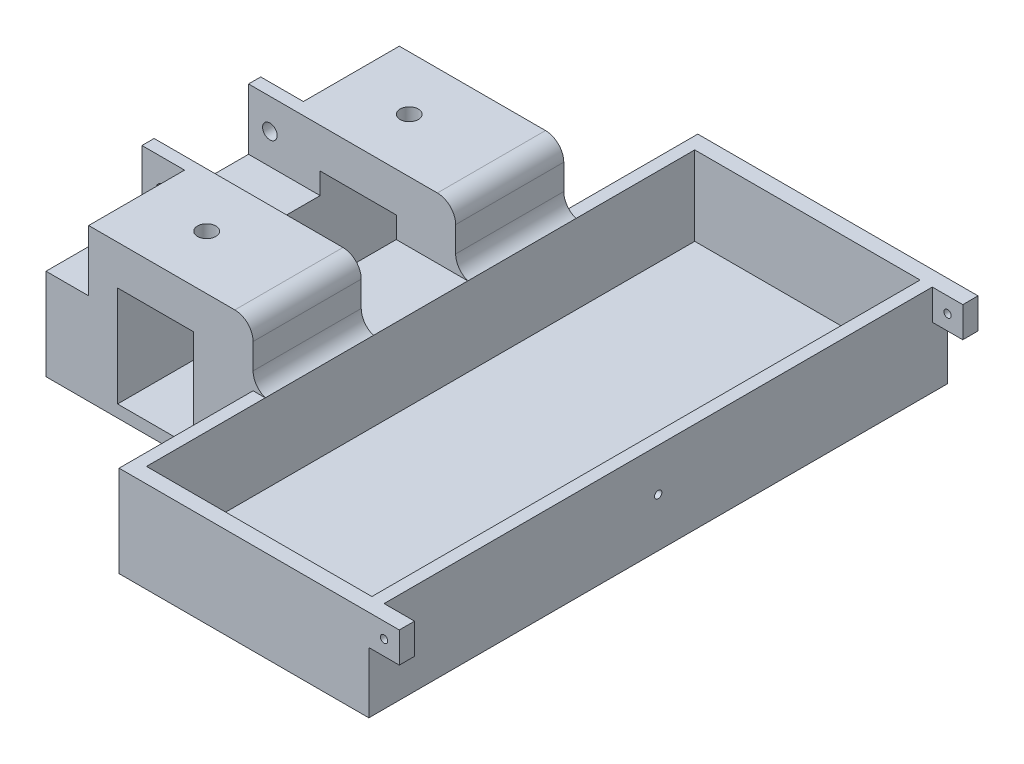
SolidWorks part; units mm, degrees
ref_plane "Front Plane" through (0, 0, 0) normal (0, 0, 1) x (1, 0, 0)
ref_plane "Top Plane" through (0, 0, 0) normal (0, 1, 0) x (1, 0, 0)
ref_plane "Right Plane" through (0, 0, 0) normal (1, 0, 0) x (0, 0, -1)
sketch "Sketch1" plane through (0, 0, 0) normal (0, 1, 0) x (1, 0, 0)
  line L1 (-37.5, -47.5) -> (37.5, -47.5)
  line L2 (-37.5, -47.5) -> (-37.5, 47.5)
  line L3 (-37.5, 47.5) -> (37.5, 47.5)
  line L4 (37.5, -47.5) -> (37.5, 47.5)
  line L5 (-37.5, -47.5) -> (37.5, 47.5) construction
  line L6 (-37.5, 47.5) -> (37.5, -47.5) construction
  point P0 (0, 0)
  dimension "D1" = 75
  dimension "D2" = 95
extrude "Boss-Extrude1" add sketch "Sketch1" along normal blind 15
sketch "Sketch2" plane through (37.5, 0, 0) normal (1, 0, 0) x (0, 0, -1)
  line L0 (47.5, 15) -> (47.5, 0) construction
  line L1 (-47.5, 15) -> (47.5, 15)
  line L2 (-47.5, 15) -> (-47.5, 10)
  line L3 (-47.5, 10) -> (47.5, 10)
  line L4 (47.5, 15) -> (47.5, 10)
  dimension "D1" = 5
extrude "Boss-Extrude2" add sketch "Sketch2" along normal blind 5
sketch "Sketch3" plane through (0, 0, -47.5) normal (0, 0, -1) x (-1, 0, 0)
  line L0 (-42.5, 10) -> (-42.5, 15) construction
  circle A0 centre (-40, 12.4586) radius 0.6
  point P2 (-42.5, 12.5)
  dimension "D1" = 2.5
extrude "Cut-Extrude1" cut sketch "Sketch3" against normal blind 100
sketch "Sketch4" plane through (0, 15, 0) normal (0, 1, 0) x (1, 0, 0)
  line L0 (42.5, 47.5) -> (42.5, -47.5) construction
  line L1 (42.5, -45) -> (37.5, -45)
  line L2 (42.5, -45) -> (42.5, 45)
  line L3 (42.5, 45) -> (37.5, 45)
  line L4 (37.5, -45) -> (37.5, 45)
  dimension "D1" = 5
  dimension "D2" = 2.5
  dimension "D3" = 2.5
extrude "Cut-Extrude2" cut sketch "Sketch4" against normal blind 100
sketch "Sketch5" plane through (0, 0, -47.5) normal (0, 0, -1) x (-1, 0, 0)
  line L0 (-37.5, 0) -> (37.5, 0) construction
  line L1 (37.5, 15) -> (3.5, 15)
  line L2 (37.5, 15) -> (37.5, 0)
  line L3 (37.5, 0) -> (3.5, 0)
  line L4 (3.5, 15) -> (3.5, 0)
  dimension "D1" = 34
extrude "Cut-Extrude3" cut sketch "Sketch5" against normal blind 22
sketch "Sketch6" plane through (0, 0, 47.5) normal (0, 0, 1) x (1, 0, 0)
  line L0 (-37.5, 0) -> (37.5, 0) construction
  line L1 (-37.5, 15) -> (-3.5, 15)
  line L2 (-37.5, 15) -> (-37.5, 0)
  line L3 (-37.5, 0) -> (-3.5, 0)
  line L4 (-3.5, 15) -> (-3.5, 0)
  dimension "D1" = 34
extrude "Cut-Extrude4" cut sketch "Sketch6" against normal blind 22
sketch "Sketch7" plane through (0, 15, 0) normal (0, 1, 0) x (1, 0, 0)
  line L0 (-3.5, -25.5) -> (-3.5, -47.5) construction
  line L1 (-1.5, -45) -> (35.5, -45)
  line L2 (-1.5, -45) -> (-1.5, 45)
  line L3 (-1.5, 45) -> (35.5, 45)
  line L4 (35.5, -45) -> (35.5, 45)
  line L5 (-3.5, -47.5) -> (42.5, -47.5) construction
  line L6 (42.5, 47.5) -> (-3.5, 47.5) construction
  point P8 (37.5, 45)
  dimension "D1" = 2
  dimension "D2" = 2.5
  dimension "D3" = 2.5
  dimension "D4" = 2
extrude "Cut-Extrude5" cut sketch "Sketch7" against normal blind 13
sketch "Sketch10" plane through (0, 15, 0) normal (0, 1, 0) x (1, 0, 0)
  line L1 (-37.5, 25.5) -> (-3.5, 25.5)
  line L2 (-37.5, 25.5) -> (-37.5, -25.5)
  line L3 (-37.5, -25.5) -> (-3.5, -25.5)
  line L4 (-3.5, 25.5) -> (-3.5, -25.5)
extrude "Boss-Extrude3" add sketch "Sketch10" along normal blind 10
sketch "Sketch11" plane through (0, 0, 25.5) normal (0, 0, 1) x (1, 0, 0)
  line L0 (-37.5, 0) -> (-3.5, 0) construction
  line L1 (-25.75, 2) -> (-13.25, 2)
  line L2 (-25.75, 2) -> (-25.75, 18.5)
  line L3 (-25.75, 18.5) -> (-13.25, 18.5)
  line L4 (-13.25, 2) -> (-13.25, 18.5)
  line L5 (-37.5, 25) -> (-37.5, 0) construction
  dimension "D1" = 12.5
  dimension "D2" = 16.5
  dimension "D3" = 2
  dimension "D4" = 11.75
extrude "Cut-Extrude6" cut sketch "Sketch11" against normal blind 100
sketch "Sketch12" plane through (-37.5, 0, 0) normal (-1, 0, 0) x (0, 0, 1)
  line L4 (7.75, 25) -> (7.75, 15)
  line L8 (-7.75, 25) -> (-7.75, 15)
  line L9 (-7.75, 15) -> (7.75, 15)
  line L11 (-7.75, 25) -> (7.75, 25)
  dimension "D1" = 15.5
  dimension "D2" = 10
extrude "Cut-Extrude8" cut sketch "Sketch12" against normal blind 100
sketch "Sketch13" plane through (-37.5, 0, 0) normal (-1, 0, 0) x (0, 0, 1)
  line L1 (-25.5, 25) -> (-9.75, 25)
  line L2 (-25.5, 25) -> (-25.5, 15)
  line L3 (-25.5, 15) -> (-9.75, 15)
  line L4 (-9.75, 25) -> (-9.75, 15)
  dimension "D1" = 15.75
extrude "Cut-Extrude9" cut sketch "Sketch13" against normal blind 7
sketch "Sketch14" plane through (-37.5, 0, 0) normal (-1, 0, 0) x (0, 0, 1)
  line L1 (25.5, 25) -> (9.75, 25)
  line L2 (25.5, 25) -> (25.5, 15)
  line L3 (25.5, 15) -> (9.75, 15)
  line L4 (9.75, 25) -> (9.75, 15)
  dimension "D1" = 10
  dimension "D2" = 2
extrude "Cut-Extrude10" cut sketch "Sketch14" against normal blind 7
sketch "Sketch15" plane through (0, 0, 9.75) normal (0, 0, 1) x (1, 0, 0)
  line L0 (-30.5, 15) -> (-37.5, 15) construction
  line L1 (-30.5, 25) -> (-30.5, 15) construction
  circle A0 centre (-34, 20) radius 1.2
  point P6 (-31.5863, 18.7429)
  dimension "D1" = 5
  dimension "D2" = 3.5
extrude "Cut-Extrude11" cut sketch "Sketch15" against normal blind 100
sketch "Sketch16" plane through (0, 2, 0) normal (0, 1, 0) x (1, 0, 0)
  line L0 (-1.5, -45) -> (35.5, -45) construction
  line L1 (33.5, -43) -> (28.5, -43)
  line L2 (33.5, -43) -> (33.5, -33)
  line L3 (33.5, -33) -> (28.5, -33)
  line L4 (28.5, -43) -> (28.5, -33)
  line L5 (35.5, 45) -> (-1.5, 45) construction
  line L6 (33.5, 43) -> (28.5, 43)
  line L7 (33.5, 43) -> (33.5, 33)
  line L8 (33.5, 33) -> (28.5, 33)
  line L9 (28.5, 43) -> (28.5, 33)
  line L10 (35.5, -45) -> (35.5, 45) construction
  line L11 (35.5, -45) -> (35.5, 45) construction
  circle A0 centre (31, 30) radius 1.2
  circle A1 centre (31, -30) radius 1.2
  dimension "D9" = 3
  dimension "D11" = 3
  dimension "D1" = 5
  dimension "D2" = 10
  dimension "D3" = 2
  dimension "D4" = 5
  dimension "D5" = 10
  dimension "D6" = 2
  dimension "D7" = 2
  dimension "D8" = 2
  dimension "D10" = 4.5
extrude "Cut-Extrude12" cut sketch "Sketch16" against normal blind 100
sketch "Sketch17" plane through (0, 25, 0) normal (0, 1, 0) x (1, 0, 0)
  line L1 (-30.5, -25.5) -> (-3.5, -25.5) construction
  line L3 (-3.5, 25.5) -> (-30.5, 25.5) construction
  circle A0 centre (-20, -16.625) radius 1.5
  circle A1 centre (-20, 16.625) radius 1.5
  dimension "D1" = 5.75
  dimension "D3" = 8.875
  dimension "D4" = 3
  dimension "D2" = 8.875
extrude "Cut-Extrude14" cut sketch "Sketch17" against normal blind 10
fillet "Fillet3" radius 3 2 edges at (-3.5, 15, -16.625) (-3.5, 25, -16.625)
fillet "Fillet4" radius 3 2 edges at (-3.5, 25, 16.625) (-3.5, 15, 16.625)
sketch "Sketch19" plane through (37.5, 0, 0) normal (1, 0, 0) x (0, 0, -1)
  line L0 (47.5, 10) -> (47.5, 0) construction
  line L1 (45, 15) -> (-45, 15) construction
  circle A0 centre (0, 8) radius 0.6
  point P2 (47.5, 5)
  point P5 (0, 15)
  dimension "D1" = 47.5
  dimension "D2" = 7
extrude "Cut-Extrude15" cut sketch "Sketch19" against normal blind 10
